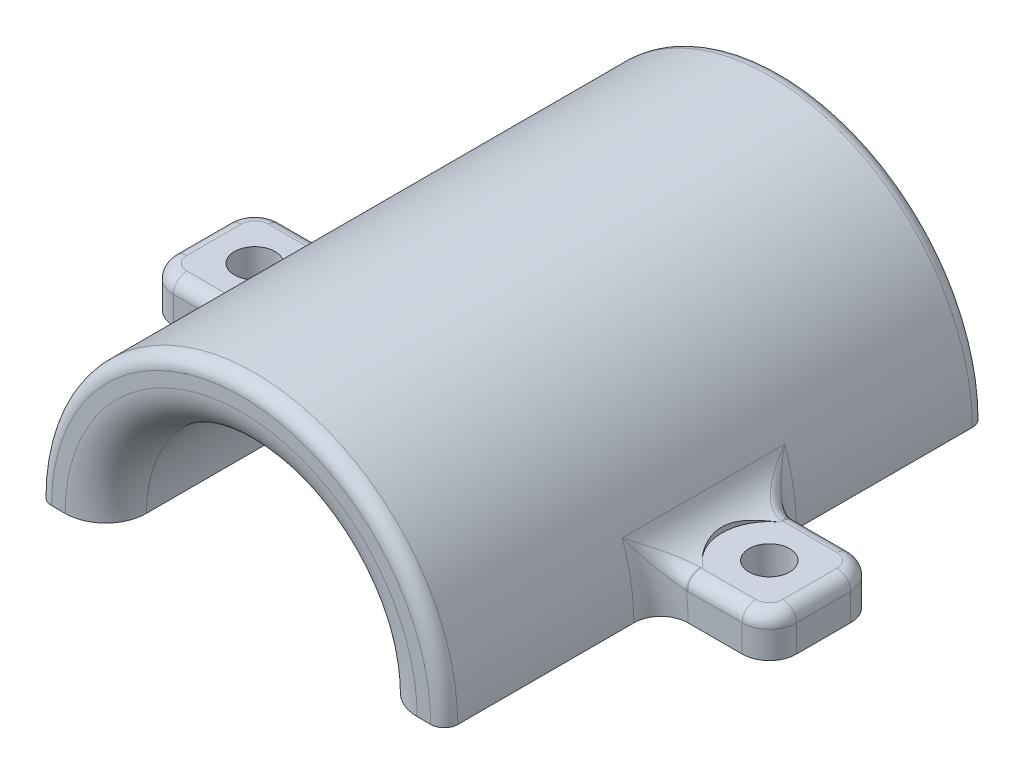
SolidWorks part; units mm, degrees
material "ABS"
ref_plane "Front Plane" through (0, 0, 0) normal (0, 0, 1) x (1, 0, 0)
ref_plane "Top Plane" through (0, 0, 0) normal (0, 1, 0) x (1, 0, 0)
ref_plane "Right Plane" through (0, 0, 0) normal (1, 0, 0) x (0, 0, -1)
sketch "Sketch1" plane through (0, 0, 0) normal (0, 0, 1) x (1, 0, 0)
  line L0 (-10, 0) -> (10, 0)
  line L1 (-15, 0) -> (15, 0)
  arc A0 (-10, 0) -> (10, 0) centre (0, 0) cw
  arc A1 (-15, 0) -> (15, 0) centre (0, 0) cw
  point P4 (0, 0)
  point P9 (0, 0)
  dimension "D2" = 5
  dimension "D1" = 20
extrude "Boss-Extrude1" add sketch "Sketch1" along normal blind 40 contours A1 L1 A0 region at (-12.5, 0.3354, 0)
sketch "Sketch2" plane through (0, 0, 0) normal (0, -1, 0) x (1, 0, 0)
  line L0 (-15, 40) -> (-15, 0) construction
  line L1 (-10, 24) -> (-23, 24)
  line L2 (-10, 24) -> (-10, 16)
  line L3 (-10, 16) -> (-23, 16)
  line L4 (-23, 24) -> (-23, 16)
  line L5 (15, 0) -> (15, 40) construction
  line L6 (-10, 40) -> (-10, 0) construction
  circle A0 centre (-19, 20) radius 1.5
  point P10 (-23, 20)
  point P14 (15, 20)
  point P15 (-10, 20)
  dimension "D1" = 3
  dimension "D2" = 4
  dimension "D3" = 4
  dimension "D4" = 4
extrude "Boss-Extrude2" add sketch "Sketch2" against normal blind 3
mirror "Mirror1" about plane through (0, 0, 0) normal (1, 0, 0) of "Boss-Extrude2"
fillet "Fillet1" radius 3 4 edges at (0, 10, 0) (14.6969, 3, 20) (-14.6969, 3, 20) (0, 10, 40)
fillet "Fillet2" radius 2 4 edges at (-23, 1.5, 24) (-23, 1.5, 16) (23, 1.5, 16) (23, 1.5, 24)
fillet "Fillet3" radius 2 4 edges at (-14.784, 2.5365, 16) (14.784, 2.5365, 16) (14.784, 2.5365, 24) (-14.784, 2.5365, 24)
fillet "Fillet4" radius 1 20 edges at (-15.3779, 3.4577, 15.5706) (-16.8509, 3.0024, 16) (-18.9853, 3, 16) (-22.4142, 3, 16.5858) (-23, 3, 20) (-22.4142, 3, 23.4142) (-18.9853, 3, 24) (15.3779, 3.4577, 15.5706) (16.8509, 3.0024, 16) (18.9853, 3, 16) (22.4142, 3, 16.5858) (23, 3, 20) (22.4142, 3, 23.4142) (18.9853, 3, 24) (0, 15, 0) (0, 15, 40) (15.3779, 3.4577, 24.4294) (16.8509, 3.0024, 24) (-15.3779, 3.4577, 24.4294) (-16.8509, 3.0024, 24)
sketch "Sketch3" plane through (0, 3, 0) normal (0, 1, 0) x (1, 0, 0)
  circle A0 centre (-19, -20) radius 3.5
  point P3 (0, 0)
  point P4 (-19, -20)
  dimension "D1" = 7
extrude "Cut-Extrude1" cut sketch "Sketch3" along normal through all
mirror "Mirror3" about plane through (0, 0, 0) normal (1, 0, 0) of "Cut-Extrude1"
